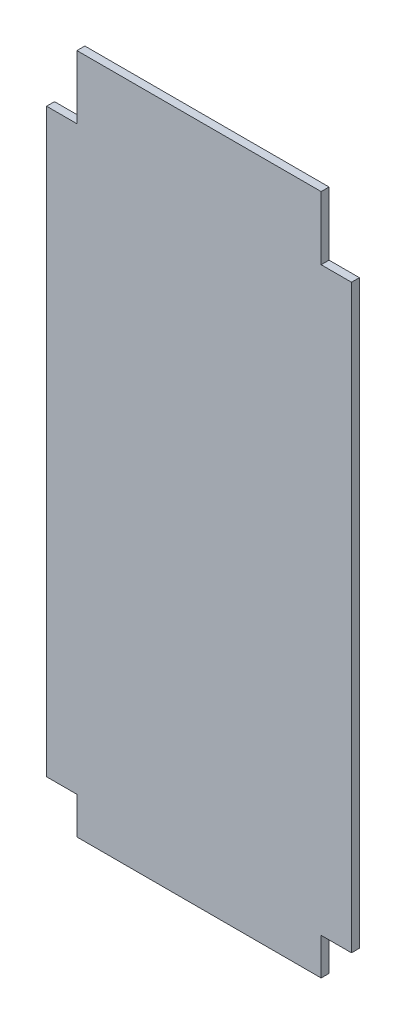
SolidWorks part; units mm, degrees
ref_plane "Front Plane" through (0, 0, 0) normal (0, 0, 1) x (1, 0, 0)
ref_plane "Top Plane" through (0, 0, 0) normal (0, 1, 0) x (1, 0, 0)
ref_plane "Right Plane" through (0, 0, 0) normal (1, 0, 0) x (0, 0, -1)
sketch "Sketch1" plane through (0, 0, 0) normal (0, 0, 1) x (1, 0, 0)
  line L0 (96.8148, -418.5873) -> (96.8148, -390.5873)
  line L2 (-111.1852, 49.4127) -> (-111.1852, -390.5873)
  line L3 (-88.1852, -418.5873) -> (96.8148, -418.5873)
  line L4 (119.8148, 49.4127) -> (119.8148, -390.5873)
  line L5 (96.8148, -390.5873) -> (119.8148, -390.5873)
  line L6 (-88.1852, -418.5873) -> (-88.1852, -390.5873)
  line L7 (-88.1852, -390.5873) -> (-111.1852, -390.5873)
  line L8 (-111.1852, 49.4127) -> (-88.1852, 49.4127)
  line L9 (-88.1852, 49.4127) -> (-88.1852, 97.4127)
  line L10 (96.8148, 97.4127) -> (96.8148, 49.4127)
  line L11 (96.8148, 49.4127) -> (119.8148, 49.4127)
  line L15 (-88.1852, 97.4127) -> (96.8148, 97.4127)
  dimension "D1" = 231
  dimension "D2" = 48
  dimension "D3" = 23
  dimension "D4" = 28
extrude "Boss-Extrude1" add sketch "Sketch1" along normal blind 6
